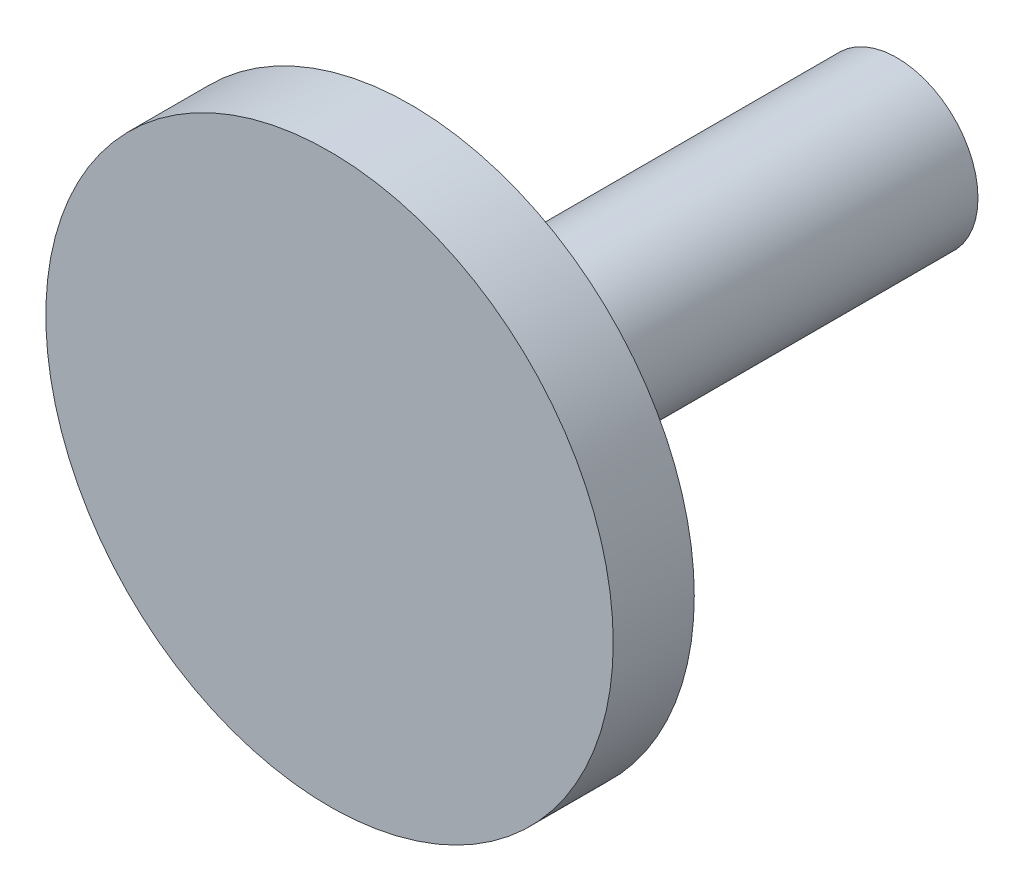
SolidWorks part; units mm, degrees
ref_plane "Front Plane" through (0, 0, 0) normal (0, 0, 1) x (1, 0, 0)
ref_plane "Top Plane" through (0, 0, 0) normal (0, 1, 0) x (1, 0, 0)
ref_plane "Right Plane" through (0, 0, 0) normal (1, 0, 0) x (0, 0, -1)
sketch "Sketch1" plane through (0, 0, 0) normal (0, 0, 1) x (1, 0, 0)
  circle A0 centre (0, 0) radius 17.5
  circle A1 centre (0, 0) radius 5
  dimension "D1" = 35
  dimension "D2" = 10
extrude "Boss-Extrude1" add sketch "Sketch1" along normal blind 5 contours A0
extrude "Boss-Extrude2" add sketch "Sketch1<3>" against normal blind 30 contours A1
sketch "Sketch1<3>" plane through (0, 0, 0) normal (0, 0, 1) x (1, 0, 0) same geometry as "Sketch1"
